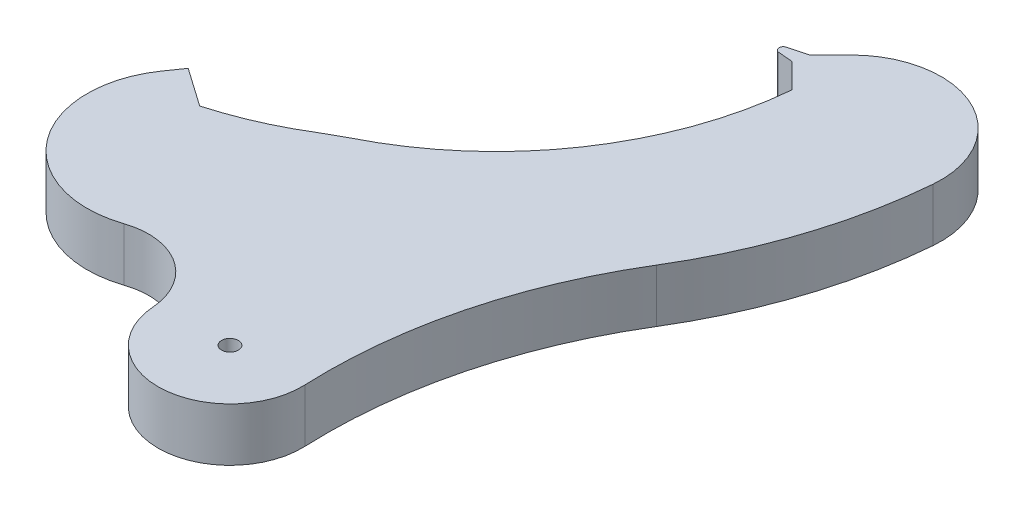
SolidWorks part; units mm, degrees
ref_plane "Front Plane" through (0, 0, 0) normal (0, 0, 1) x (1, 0, 0)
ref_plane "Top Plane" through (0, 0, 0) normal (0, 1, 0) x (1, 0, 0)
ref_plane "Right Plane" through (0, 0, 0) normal (1, 0, 0) x (0, 0, -1)
sketch "Sketch1" plane through (0, 0, 0) normal (0, 1, 0) x (1, 0, 0)
  line L0 (0, 0) -> (33.1203, 0)
  line L1 (33.1203, 0) -> (34.952, 1.8318)
  line L2 (0, 0) -> (32.9388, 3.462)
  line L3 (34.952, 1.8318) -> (32.9388, 3.462)
  dimension "D1" = 84
  dimension "D2" = 6
  dimension "D3" = 35
sketch "Sketch3" plane through (0, 0, 0) normal (0, 1, 0) x (1, 0, 0)
  line L0 (34.4081, 0.9343) -> (36.7664, 3.2926)
  line L1 (33.9922, -0.5183) -> (36.846, -3.3722)
  line L2 (0.6361, -35.4601) -> (2.7509, -36.9409) construction
  line L3 (0.6361, -35.4601) -> (-0.8777, -37.622) construction
  line L4 (30, -60) -> (30, 1.6219) construction
  line L5 (33.1203, 0) -> (34.8881, 0) construction
  line L8 (30, -60) -> (4.8643, -34.6537) construction
  line L9 (30, -60) -> (2.7509, -36.9409) construction
  line L10 (0.6361, -35.4601) -> (-0.5111, -37.0984)
  line L11 (0.6361, -35.4601) -> (4.9163, -38.4572)
  line L12 (2.8866, -32.9942) -> (1.1902, -35.016) construction
  line L13 (2.8866, -32.9942) -> (4.8643, -34.6537) construction
  line L15 (2.8866, -32.9942) -> (3.462, -32.9388) construction
  line L16 (0, -33.1203) -> (0.578, -33.1152) construction
  line L17 (0.578, -33.1152) -> (1.1559, -33.1001) construction
  line L18 (1.1559, -33.1001) -> (1.7334, -33.0749) construction
  line L19 (1.7334, -33.0749) -> (2.3104, -33.0396) construction
  line L20 (2.3104, -33.0396) -> (2.8866, -32.9942) construction
  line L21 (30, -60) -> (0, 0) construction
  line L22 (14.2531, -34.3687) -> (16.5469, -33.0938)
  line L23 (33.9922, -0.5183) -> (32.3376, -0.3736)
  line L24 (34.4081, 0.9343) -> (32.2732, 0.3622)
  line L25 (30, -60) -> (-5.1152, -2.843) construction
  line L26 (35.772, -9.4534) -> (52.2077, -13.7968) construction
  circle A0 centre (30, -60) radius 0.95
  arc A1 (36.846, -3.3722) -> (16.5469, -33.0938) centre (0, 0) cw
  circle A2 centre (30, -60) radius 35.7445 construction
  arc A3 (0, -33.1203) -> (3.462, -32.9388) centre (0, 0) ccw construction
  arc A4 (32.3376, -0.3736) -> (32.2732, 0.3622) centre (32.3703, 0) cw
  arc A5 (36.7664, 3.2926) -> (53.8005, -4.6373) centre (43.8375, -3.7785) cw
  arc A6 (-0.5111, -37.0984) -> (12.15, -54.0085) centre (8.5956, -43.4749) ccw
  arc A7 (4.9163, -38.4572) -> (14.2531, -34.3687) centre (-5.1152, -2.843) ccw
  arc A8 (53.8005, -4.6373) -> (24.1495, -48.2991) centre (0, 0) cw construction
  arc A9 (12.15, -54.0085) -> (23.152, -48.8535) centre (-5.1152, -2.843) ccw construction
  arc A10 (12.15, -54.0085) -> (22.0205, -60.5726) centre (14.546, -61.109) cw
  arc A11 (37.9925, -59.6537) -> (46.116, -28.0947) centre (93.94, -57.23) cw
  arc A12 (53.8005, -4.6373) -> (46.116, -28.0947) centre (0, 0) cw
  arc A13 (37.9925, -59.6537) -> (22.0205, -60.5726) centre (30, -60) cw
  dimension "D5" = 0.375
  dimension "D14" = 37
  dimension "D17" = 10
  dimension "D18" = 54
  dimension "D19" = 8
  dimension "D20" = 56
  dimension "D21" = 1.9
  dimension "D1" = 30
  dimension "D2" = 60
  dimension "D6" = 15
  dimension "D7" = 5
  dimension "D8" = 0.75
  dimension "D4" = 5
  dimension "D11" = 35.6965
  dimension "D13" = 2
  dimension "D15" = 5
  dimension "D16" = 17
  dimension "D12" = 2
extrude "Boss-Extrude2" add sketch "Sketch3" along normal blind 6
sketch "Sketch4" plane through (0, 6, 0) normal (0, 1, 0) x (1, 0, 0)
  line L14 (36.6957, 3.3633) -> (34.3563, 1.0239)
  line L15 (34.3563, 1.0239) -> (32.2473, 0.4588)
  line L16 (32.3289, -0.4732) -> (33.9472, -0.6148)
  line L17 (33.9472, -0.6148) -> (36.7421, -3.4097)
  line L18 (16.5002, -33.0053) -> (14.2026, -34.2824)
  line L19 (4.9348, -38.348) -> (0.6115, -35.3208)
  line L20 (0.6115, -35.3208) -> (-0.593, -37.041)
  line L21 (36.6957, 3.3633) -> (34.3563, 1.0239)
  line L22 (34.3563, 1.0239) -> (32.2473, 0.4588)
  line L23 (32.3289, -0.4732) -> (33.9472, -0.6148)
  line L24 (33.9472, -0.6148) -> (36.7421, -3.4097)
  line L25 (16.5002, -33.0053) -> (14.2026, -34.2824)
  line L26 (4.9348, -38.348) -> (0.6115, -35.3208)
  line L27 (0.6115, -35.3208) -> (-0.593, -37.041)
  circle A9 centre (30, -60) radius 0.95
  circle A10 centre (30, -60) radius 0.95 construction
  arc A18 (53.9001, -4.6458) -> (36.6957, 3.3633) centre (43.8375, -3.7785) ccw
  arc A19 (32.2473, 0.4588) -> (32.3289, -0.4732) centre (32.3703, 0) ccw
  arc A20 (16.5002, -33.0053) -> (36.7421, -3.4097) centre (0, 0) ccw
  arc A21 (4.9348, -38.348) -> (14.2026, -34.2824) centre (-5.1152, -2.843) ccw
  arc A22 (-0.593, -37.041) -> (12.182, -54.1033) centre (8.5956, -43.4749) ccw
  arc A23 (21.9208, -60.5798) -> (12.182, -54.1033) centre (14.546, -61.109) ccw
  arc A24 (21.9208, -60.5798) -> (38.0924, -59.6494) centre (30, -60) ccw
  arc A25 (46.2014, -28.1467) -> (38.0924, -59.6494) centre (93.94, -57.23) ccw
  arc A26 (46.2014, -28.1467) -> (53.9001, -4.6458) centre (0, 0) ccw
  arc A27 (53.9001, -4.6458) -> (36.6957, 3.3633) centre (43.8375, -3.7785) ccw
  arc A28 (32.2473, 0.4588) -> (32.3289, -0.4732) centre (32.3703, 0) ccw
  arc A29 (16.5002, -33.0053) -> (36.7421, -3.4097) centre (0, 0) ccw
  arc A30 (4.9348, -38.348) -> (14.2026, -34.2824) centre (-5.1152, -2.843) ccw
  arc A31 (-0.593, -37.041) -> (12.182, -54.1033) centre (8.5956, -43.4749) ccw
  arc A32 (21.9208, -60.5798) -> (12.182, -54.1033) centre (14.546, -61.109) ccw
  arc A33 (21.9208, -60.5798) -> (38.0924, -59.6494) centre (30, -60) ccw
  arc A34 (46.2014, -28.1467) -> (38.0924, -59.6494) centre (93.94, -57.23) ccw
  arc A35 (46.2014, -28.1467) -> (53.9001, -4.6458) centre (0, 0) ccw
  dimension "D1" = 0.1
extrude "Boss-Extrude3" add sketch "Sketch4" against normal up to surface (6 mm away) up to face at (25.9976, 0, 24.5014)
